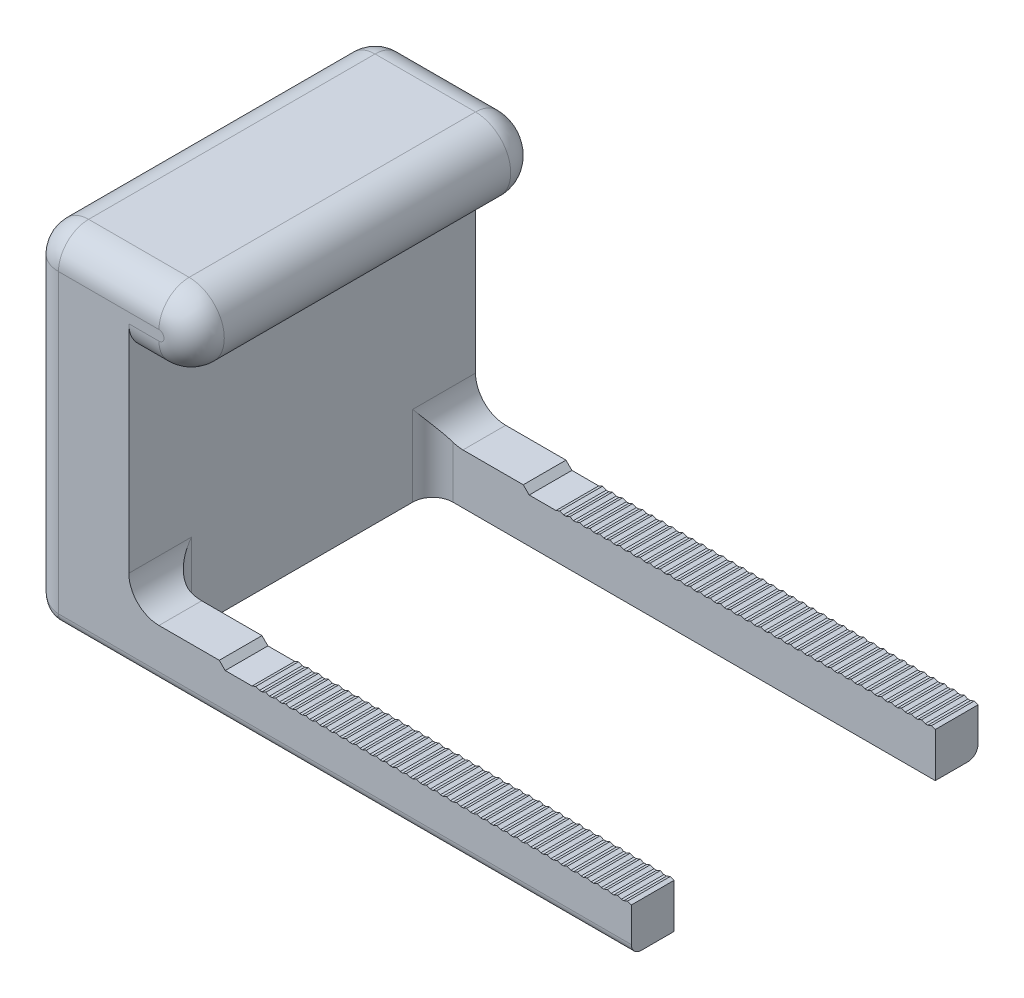
SolidWorks part; units mm, degrees
ref_plane "Front" through (0, 0, 0) normal (0, 0, 1) x (1, 0, 0)
ref_plane "Top" through (0, 0, 0) normal (0, 1, 0) x (1, 0, 0)
ref_plane "Right" through (0, 0, 0) normal (1, 0, 0) x (0, 0, -1)
sketch "Sketch1" plane through (0, 0, 0) normal (0, 1, 0) x (1, 0, 0)
  line L0 (0, 13) -> (0, -13)
  line L1 (0, 17.25) -> (-10, 17.25)
  line L2 (0, -17.25) -> (-10, -17.25)
  line L3 (-10, 17.25) -> (-10, -17.25)
  line L5 (0, 17.25) -> (50, 17.25)
  line L6 (0, 13) -> (50, 13)
  line L7 (50, 17.25) -> (50, 13)
  line L9 (0, -17.25) -> (50, -17.25)
  line L10 (0, -13) -> (50, -13)
  line L11 (50, -17.25) -> (50, -13)
  point P0 (0, 0)
  dimension "D1" = 10
  dimension "D2" = 4.25
  dimension "D3" = 26
  dimension "D4" = 50
extrude "Boss-Extrude1" add sketch "Sketch1" along normal blind 5
sketch "Sketch2" plane through (0, 5, 0) normal (0, 1, 0) x (1, 0, 0)
  line L0 (-10, -17.25) -> (50, -17.25) construction
  line L1 (-10, 17.25) -> (0, 17.25)
  line L2 (-10, 17.25) -> (-10, -17.25)
  line L3 (-10, -17.25) -> (0, -17.25)
  line L4 (0, 17.25) -> (0, -17.25)
  line L5 (0, -13) -> (0, 13) construction
extrude "Boss-Extrude2" add sketch "Sketch2" along normal blind 28.5
fillet "Fillet1" radius 3 2 edges at (0, 5, -15.125) (0, 5, 15.125)
fillet "Fillet2" radius 2 2 edges at (0, 4, 13) (0, 4, -13)
sketch "Sketch4" plane through (0, 0, 17.25) normal (0, 0, 1) x (1, 0, 0)
  line L1 (3, 26.5) -> (0, 26.5)
  line L2 (0, 33.5) -> (0, 8) construction
  line L3 (0, 26.5) -> (0, 33.5)
  line L4 (0, 33.5) -> (3, 33.5)
  arc A0 (3, 33.5) -> (3, 26.5) centre (3, 30) cw
  dimension "D1" = 7
  dimension "D2" = 3
extrude "Boss-Extrude3" add sketch "Sketch4" against normal up to surface (34.5 mm away) up to face at (11.7684, 12.0541, -17.25)
sketch "Sketch6" plane through (0, 0, 17.25) normal (0, 0, 1) x (1, 0, 0)
  line L0 (10, 4.41) -> (50, 4.41)
  line L1 (50, 5) -> (10, 5)
  line L4 (10, 5) -> (10, 4.41)
  line L5 (50, 5) -> (50, 0) construction
  line L6 (50, 4.41) -> (50, 5)
  dimension "D1" = 0.59
  dimension "D2" = 40
extrude "Cut-Extrude1" cut sketch "Sketch6" against normal through all
sketch "Sketch8" plane through (0, 0, 17.25) normal (0, 0, 1) x (1, 0, 0)
  line L0 (50, 4.41) -> (49.26, 4.41)
  line L1 (10, 4.41) -> (50, 4.41) construction
  line L2 (49.26, 4.41) -> (49.63, 4.56)
  line L3 (49.63, 4.56) -> (50, 4.41)
  dimension "D1" = 0.15
  dimension "D2" = 0.74
extrude "Boss-Extrude4" add sketch "Sketch8" against normal up to surface (34.5 mm away) up to face at (10.1708, 13.2908, -17.25)
pattern_linear "LPattern1" count 38 spacing 1 along (-1, 0, 0) of "Boss-Extrude4"
sketch "Sketch9" plane through (0, 4.41, 0) normal (0, -1, 0) x (1, 0, 0)
  line L0 (2, -13) -> (50, -13) construction
  line L1 (50, 13) -> (9.6113, 13)
  line L2 (50, 13) -> (50, -13)
  line L3 (50, -13) -> (9.6113, -13)
  line L4 (9.6113, 13) -> (9.6113, -13)
extrude "Cut-Extrude2" cut sketch "Sketch9" against normal blind 1
chamfer "Chamfer1" distance 1 angle 45 2 edges at (10, 5, 15.125) (10, 5, -15.125)
fillet "Fillet3" radius 3 4 edges at (-10, 33.5, 0) (-10, 16.75, -17.25) (-10, 16.75, 17.25) (-10, 0, 0)
fillet "Fillet4" radius 3 8 edges at (1.5, 26.5, -17.25) (6.5, 30, -17.25) (-9.1213, 32.6213, -16.3713) (-9.1213, 32.6213, 16.3713) (1.5, 26.5, 17.25) (6.5, 30, 17.25) (-2, 33.5, -17.25) (-2, 33.5, 17.25)
fillet "Fillet5" radius 1 4 edges at (-9.1213, 0.8787, 16.3713) (21.5, 0, 17.25) (-9.1213, 0.8787, -16.3713) (21.5, 0, -17.25)
